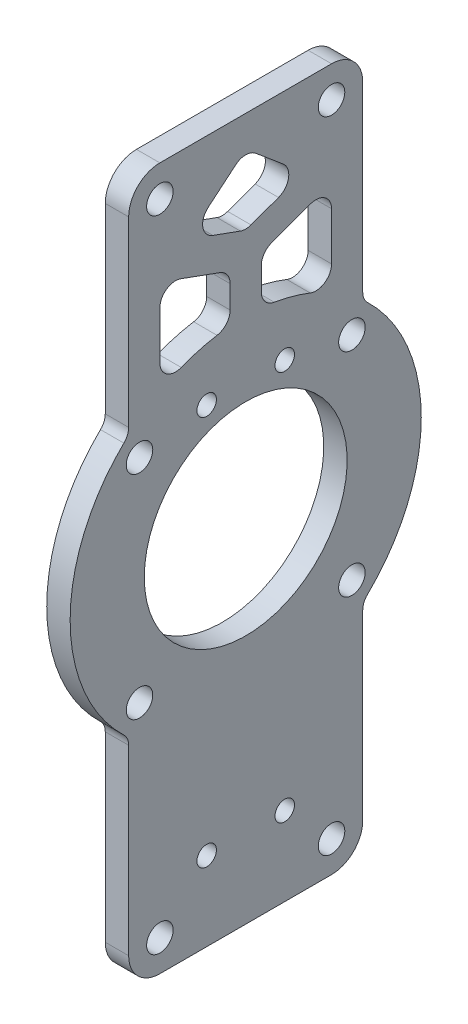
SolidWorks part; units mm, degrees
material "Сплав 2024"
ref_plane "Спереди" through (0, 0, 0) normal (0, 0, 1) x (1, 0, 0)
ref_plane "Сверху" through (0, 0, 0) normal (0, 1, 0) x (1, 0, 0)
ref_plane "Справа" through (0, 0, 0) normal (1, 0, 0) x (0, 0, -1)
sketch "Эскиз1" plane through (0, 0, 0) normal (0, 1, 0) x (1, 0, 0)
  line L1 (0, 0) -> (3, 0)
  line L2 (0, 0) -> (0, -30)
  line L3 (0, -30) -> (3, -30)
  line L4 (3, 0) -> (3, -30)
  dimension "D1" = 3
  dimension "D2" = 30
extrude "Бобышка-Вытянуть1" add sketch "Эскиз1" along normal blind 90
sketch "Эскиз2" plane through (0, 0, 0) normal (-1, 0, 0) x (0, 0, 1)
  line L0 (30, 45) -> (0, 45) construction
  line L1 (30, 90) -> (30, 0) construction
  line L2 (0, 90) -> (0, 0) construction
  line L3 (15, 90) -> (15, 0) construction
  line L4 (0, 90) -> (30, 90) construction
  line L5 (0, 0) -> (30, 0) construction
  circle A0 centre (15, 45) radius 22.5
  point P2 (30, 45)
  point P3 (0, 45)
  dimension "D1" = 45
extrude "Бобышка-Вытянуть2" add sketch "Эскиз2" against normal up to surface (3 mm away) up to face at (3, 45, 15)
sketch "Эскиз3" plane through (0, 0, 0) normal (-1, 0, 0) x (0, 0, 1)
  circle A0 centre (15, 45) radius 13
  dimension "D1" = 26
extrude "Вырез-Вытянуть1" cut sketch "Эскиз3" against normal through all
sketch "Эскиз4" plane through (3, 0, 0) normal (-1, 0, 0) x (0, 0, 1)
  line L0 (30.9099, 60.9099) -> (-0.9099, 29.0901) construction
  line L2 (30.9099, 29.0901) -> (-0.9099, 60.9099) construction
  line L3 (30, 45) -> (0, 45) construction
  circle A0 centre (15, 45) radius 19.25 construction
  circle A1 centre (15, 45) radius 22.5 construction
  dimension "D1" = 38.5
  dimension "D2" = 45
hole_wizard "Отверстие с зазором M31" positions "Эскиз6" profile "Эскиз5" hole size "M3" standard "Ansi Metric" end condition through all
sketch "Эскиз6" plane through (3, -25.0247, 7.2629) normal (-1, 0, 0) x (0, 0, 1)
  line L0 (23.647, 85.9346) -> (-8.1728, 54.1148) construction
  line L1 (23.647, 54.1148) -> (-8.1728, 85.9346) construction
  circle A0 centre (7.7371, 70.0247) radius 19.25 construction
  point P0 (21.3489, 83.6365)
  point P6 (-5.8747, 83.6365)
  point P10 (-5.8747, 56.4129)
  point P12 (21.3489, 56.4129)
sketch "Эскиз5" plane through (3, 58.6118, 28.6118) normal (0, 1, 0) x (0, 0, -1)
  line L0 (0, 0) -> (0, 3)
  line L1 (0, 3) -> (1.7, 3)
  line L2 (1.7, 3) -> (1.7, 0)
  line L5 (1.7, 0) -> (0, 0)
  line L11 (0, -6.35) -> (0, 107.95) construction
  dimension "Диаметр сквозного отверстия" = 3.4
  dimension "Глубина сквозного отверстия" = 3
sketch "Эскиз8" plane through (3, 0, 0) normal (1, 0, 0) x (0, 0, -1)
  line L0 (-15, 90) -> (-15, 0) construction
  line L1 (-30, 90) -> (0, 90) construction
  line L2 (-30, 0) -> (0, 0) construction
  line L3 (19.447, 45) -> (-49.447, 45) construction
  line L4 (0, 90) -> (0, 61.7705) construction
  line L5 (-26, 86) -> (-4, 86) construction
  line L6 (-26, 86) -> (-26, 4) construction
  line L7 (-26, 4) -> (-4, 4) construction
  line L8 (-4, 86) -> (-4, 4) construction
  line L9 (-26, 86) -> (-4, 4) construction
  line L10 (-26, 4) -> (-4, 86) construction
  line L11 (0, 0) -> (-30, 0) construction
  point P8 (-15, 45)
  point P9 (-15, 45)
  dimension "D1" = 4
  dimension "D2" = 4
  dimension "D3" = 82
  dimension "D4" = 22
hole_wizard "Отверстие с зазором M32" positions "Эскиз10" profile "Эскиз9" hole size "M3" standard "Ansi Metric" end condition through all
sketch "Эскиз10" plane through (3, 0, 0) normal (1, 0, 0) x (0, 0, -1)
  point P0 (-26, 86)
  point P3 (-4, 86)
  point P6 (-4, 4)
  point P9 (-26, 4)
sketch "Эскиз9" plane through (3, 86, 26) normal (0, 1, 0) x (0, 0, -1)
  line L0 (0, 0) -> (0, 3)
  line L1 (0, 3) -> (1.7, 3)
  line L2 (1.7, 3) -> (1.7, 0)
  line L5 (1.7, 0) -> (0, 0)
  line L11 (0, -6.35) -> (0, 107.95) construction
  dimension "Диаметр сквозного отверстия" = 3.4
  dimension "Глубина сквозного отверстия" = 3
fillet "Скругление1" radius 4 4 edges at (1.5, 0, 0) (1.5, 0, 30) (1.5, 90, 30) (1.5, 90, 0)
sketch "Эскиз11" plane through (0, 0, 0) normal (1, 0, 0) x (0, 0, -1)
  line L0 (-30, 60.12) -> (0, 60.12) construction
  line L1 (-4, 0) -> (-26, 0) construction
  line L2 (0, 86) -> (0, 61.7705) construction
  line L3 (-20, 76) -> (-20, 0) construction
  line L5 (-10, 76) -> (-10, 0) construction
  line L6 (-35.3867, 10.12) -> (5.0681, 10.12) construction
  point P8 (-10, 60.12)
  point P17 (-20, 60.12)
  point P18 (-20, 10.12)
  point P19 (-10, 10.12)
  dimension "D1" = 10.12
  dimension "D2" = 10
  dimension "D3" = 10
  dimension "D4" = 50
hole_wizard "Отверстие обработанное метчиком M3x0.51" positions "Эскиз13" profile "Эскиз12" tap size "M3x0.5" standard "Ansi Metric" end condition up to next
sketch "Эскиз13" plane through (0, 0, 0) normal (-1, 0, 0) x (0, 0, 1)
  point P0 (10, 60.12)
  point P3 (20, 60.12)
  point P6 (10, 10.12)
  point P9 (20, 10.12)
sketch "Эскиз12" plane through (0, 60.12, 10) normal (0, 1, 0) x (0, 0, 1)
  line L0 (0, 0) -> (0, 3)
  line L1 (0, 3) -> (1.25, 3)
  line L2 (1.25, 3) -> (1.25, 0)
  line L5 (1.25, 0) -> (0, 0)
  line L11 (0, -6.35) -> (0, 107.95) construction
  dimension "Диаметр проходного сверла" = 2.5
  dimension "Глубина проходного сверла" = 3
cosmetic thread "Отверстие резьбы1" parameters "D2"=3
cosmetic thread "Отверстие резьбы2" parameters "D2"=3
cosmetic thread "Отверстие резьбы3" parameters "D2"=3
cosmetic thread "Отверстие резьбы4" parameters "D2"=3
sketch "Эскиз14" plane through (0, 0, 0) normal (-1, 0, 0) x (0, 0, 1)
  line L0 (4, 90) -> (4, 0) construction
  line L1 (4, 90) -> (26, 90) construction
  line L2 (4, 0) -> (26, 0) construction
  line L3 (26, 0) -> (26, 90) construction
  line L4 (0, 86) -> (0, 61.7705) construction
  line L5 (30, 86) -> (30, 61.7705) construction
  line L6 (0, 86) -> (30, 86) construction
  line L7 (13, 73.4942) -> (13, 67.4109)
  line L8 (17, 73.4942) -> (17, 67.4109)
  line L9 (15, 90) -> (15, 0) construction
  line L10 (17, 73.4942) -> (26, 76.7699)
  line L11 (26, 76.7699) -> (26, 64.6278)
  line L12 (13, 73.4942) -> (4, 76.7699)
  line L13 (4, 76.7699) -> (4, 64.6278)
  line L14 (7.5382, 79.7388) -> (15, 77.0229)
  line L15 (22.4618, 79.7388) -> (15, 77.0229)
  line L16 (4, 76.7699) -> (15, 86) construction
  line L17 (15, 86) -> (26, 76.7699) construction
  line L18 (7.5382, 79.7388) -> (15, 86)
  line L19 (15, 86) -> (22.4618, 79.7388)
  line L20 (0, 76.7699) -> (30, 76.7699) construction
  line L21 (4, 73.4942) -> (26, 73.4942) construction
  line L22 (15, 45) -> (37.5, 45) construction
  circle A0 centre (15, 45) radius 22.5 construction
  arc A1 (4, 64.6278) -> (13, 67.4109) centre (15, 45) cw
  arc A2 (17, 67.4109) -> (26, 64.6278) centre (15, 45) cw
  arc A3 (30, 28.2295) -> (30, 61.7705) centre (15, 45) ccw construction
  point P14 (4, 64.6278)
  point P15 (26, 64.6278)
  point P33 (15, 86)
  dimension "D4" = 4
  dimension "D1" = 4
  dimension "D2" = 4
  dimension "D3" = 4
  dimension "D5" = 2
  dimension "D6" = 110
  dimension "D7" = 110
  dimension "D8" = 100
  dimension "D9" = 4
extrude "Вырез-Вытянуть2" cut sketch "Эскиз14" against normal through all
fillet "Скругление2" radius 2 16 edges at (1.5, 64.6278, 26) (1.5, 67.4109, 17) (1.5, 64.6278, 4) (1.5, 67.4109, 13) (1.5, 73.4942, 17) (1.5, 76.7699, 4) (1.5, 79.7388, 7.5382) (1.5, 79.7388, 22.4618) (1.5, 77.0229, 15) (1.5, 73.4942, 13) (1.5, 76.7699, 26) (1.5, 86, 15) (1.5, 61.7705, 30) (1.5, 28.2295, 30) (1.5, 28.2295, 0) (1.5, 61.7705, 0)
